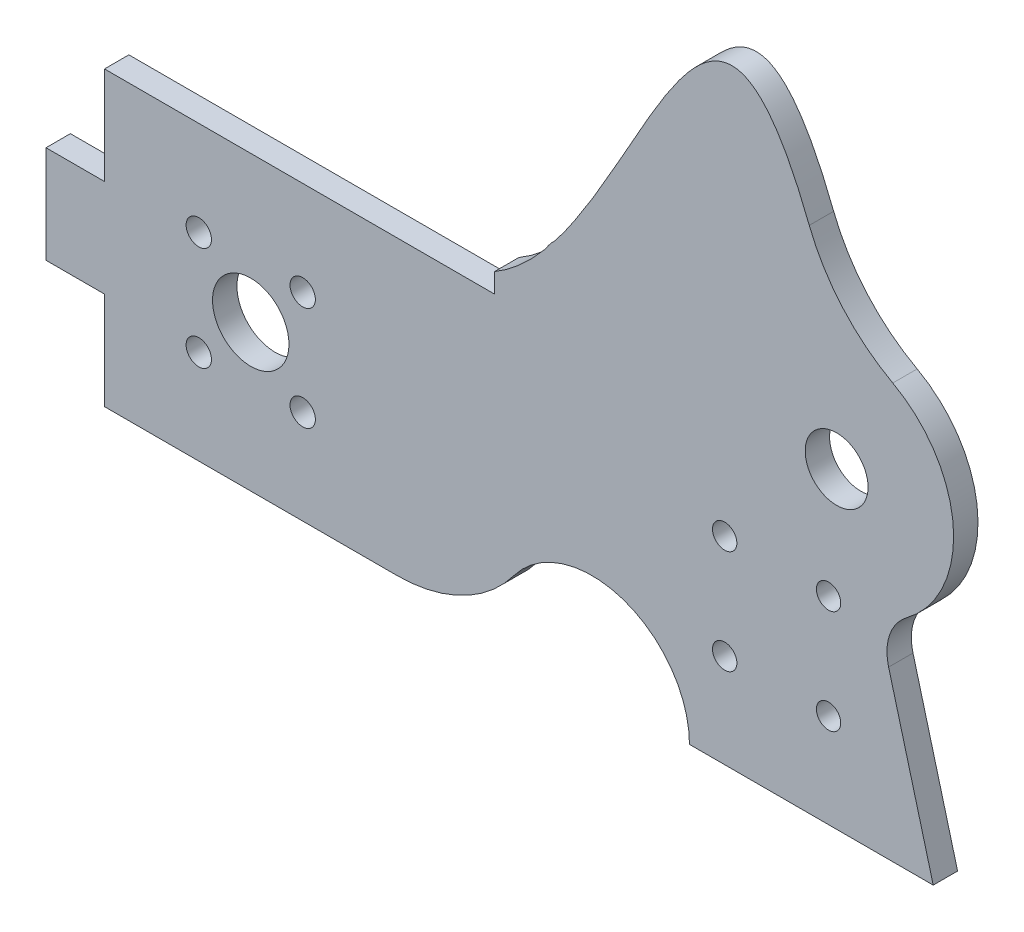
SolidWorks part; units mm, degrees
ref_plane "Front Plane" through (0, 0, 0) normal (0, 0, 1) x (1, 0, 0)
ref_plane "Top Plane" through (0, 0, 0) normal (0, 1, 0) x (1, 0, 0)
ref_plane "Right Plane" through (0, 0, 0) normal (1, 0, 0) x (0, 0, -1)
sketch "Sketch1" plane through (0, 0, 0) normal (0, 0, 1) x (1, 0, 0)
  line L0 (0, 0) -> (107.95, 0)
  line L3 (0, 38.1) -> (0, 25.4)
  line L4 (95.3675, 55.88) -> (0, 38.1)
  line L5 (0, 19.05) -> (100.2273, 19.05) construction
  line L6 (19.05, 19.05) -> (19.05, 28.62) construction
  line L7 (19.05, 19.05) -> (25.817, 25.817) construction
  line L8 (107.95, 0) -> (100.9363, 26.1756)
  line L10 (0, 12.7) -> (0, 0)
  line L11 (0, 25.4) -> (-7.62, 25.4)
  line L13 (0, 12.7) -> (-7.62, 12.7)
  line L14 (-7.62, 25.4) -> (-7.62, 12.7)
  line L15 (100.9363, 26.1756) -> (100.8688, 26.4276)
  arc A0 (100.8688, 26.4276) -> (95.3675, 55.88) centre (95.3675, 40.64) ccw
  circle A1 centre (95.3675, 40.64) radius 4.0957
  circle A2 centre (19.05, 19.05) radius 9.57 construction
  circle A3 centre (25.817, 25.817) radius 1.651
  circle A4 centre (25.817, 12.283) radius 1.651
  circle A5 centre (12.283, 12.283) radius 1.651
  circle A6 centre (12.283, 25.817) radius 1.651
  point P26 (19.05, 19.05)
  dimension "D1" = 8.1915
  dimension "D5" = 15.24
  dimension "D4" = 19.14
  dimension "D7" = 3.302
  dimension "D11" = 97.0107
  dimension "D2" = 38.1
  dimension "D3" = 40.64
  dimension "D6" = 107.95
  dimension "D8" = 45
  dimension "D9" = 4
  dimension "D10" = 19.05
  dimension "D12" = 75
  dimension "D14" = 12.7
  dimension "D15" = 12.7
  dimension "D16" = 7.62
extrude "Boss-Extrude1" add sketch "Sketch1" along normal blind 3.175
sketch "Sketch2" plane through (0, 0, 3.175) normal (0, 0, 1) x (1, 0, 0)
  circle A0 centre (95.3675, 40.64) radius 38.1 construction
sketch "Sketch6" plane through (0, 0, 3.175) normal (0, 0, 1) x (1, 0, 0)
  line L0 (0, 0) -> (107.95, 0) construction
  line L1 (50.8, 0) -> (76.2, 0)
  arc A0 (76.2, 0) -> (50.8, 0) centre (63.5, 0) ccw
  dimension "D1" = 25.4
  dimension "D2" = 31.75
extrude "Cut-Extrude2" cut sketch "Sketch6" against normal blind 6.35
sketch "Sketch7" plane through (0, 0, 3.175) normal (0, 0, 1) x (1, 0, 0)
  line L0 (12.283, 25.817) -> (25.817, 12.283) construction
  line L1 (12.283, 12.283) -> (25.817, 25.817) construction
  circle A0 centre (19.05, 19.05) radius 4.9784
  circle A2 centre (80.7829, 12.2536) radius 1.5875
  circle A3 centre (94.316, 12.2536) radius 1.5875
  circle A4 centre (80.7829, 25.7876) radius 1.5875
  circle A5 centre (94.316, 25.7876) radius 1.5875
  dimension "D1" = 9.9568
extrude "Cut-Extrude3" cut sketch "Sketch7" against normal through all
fillet "Fillet1" radius 6.35 1 edges at (100.8688, 26.4276, 1.5875)
sketch "Sketch8" plane through (0, 0, 3.175) normal (0, 0, 1) x (1, 0, 0)
  line L1 (0, 38.1) -> (50.8, 38.1)
  line L2 (0, 38.1) -> (0, 50.8)
  line L3 (0, 50.8) -> (50.8, 50.8)
  line L4 (50.8, 38.1) -> (50.8, 50.8)
  dimension "D1" = 50.8
  dimension "D2" = 12.7
extrude "Cut-Extrude4" cut sketch "Sketch8" against normal blind 50.8
sketch "Sketch9" plane through (0, 0, 3.175) normal (0, 0, 1) x (1, 0, 0)
  line L3 (50.8, 40.64) -> (57.15, 40.64)
  line L5 (57.15, 40.64) -> (50.8, 40.64)
  line L6 (57.15, 40.64) -> (57.15, 50.8)
  line L7 (57.15, 50.8) -> (50.8, 50.8)
  line L8 (50.8, 40.64) -> (50.8, 50.8)
  line L9 (0, 38.1) -> (50.8, 38.1) construction
  line M8 (50.8, 47.571) -> (50.8, 38.1)
  line M21 (95.3675, 55.88) -> (50.8, 47.571)
  dimension "D1" = 10.16
  dimension "D2" = 2.54
  dimension "D3" = 6.35
extrude "Cut-Extrude5" cut sketch "Sketch9" against normal blind 19.304 contours L3 L6 M21 M8 region at (54.0583, 44.4092, 3.175)
fillet "Fillet6" radius 6.35 1 edges at (57.15, 40.64, 1.5875)
fillet "Fillet7" radius 6.35 1 edges at (57.15, 48.7549, 1.5875)
fillet "Fillet8" radius 19.05 1 edges at (50.8, 0, 1.5875)
sketch "Sketch12" plane through (0, 0, 3.175) normal (0, 0, 1) x (1, 0, 0)
  line L0 (107.95, 0) -> (146.812, 0) construction
  line L1 (8.0257, 45.4128) -> (80.6683, 75.7903) construction
  line L2 (95.3675, 40.64) -> (80.6683, 75.7903) construction
  line L3 (80.6683, 75.7903) -> (79.4434, 78.7195) construction
  line L4 (50.8, 40.64) -> (85.0271, 40.64)
  line L5 (85.0271, 40.64) -> (95.3675, 55.88)
  arc A0 (61.8128, 49.6242) -> (56.8883, 45.1859) centre (62.9766, 43.3817) ccw construction
  circle A1 centre (19.05, 19.05) radius 28.575 construction
  circle A2 centre (95.3675, 40.64) radius 38.1 construction
  circle A3 centre (80.6683, 75.7903) radius 3.175 construction
  spline S0 degree 3 poles (50.8, 40.64) (70.7778, 52.1788) (78.5943, 111.5434) (95.3675, 55.88) knots 0 0 0 0 1 1 1 1
  dimension "D2" = 6.35
  dimension "D1" = 38.862
extrude "Boss-Extrude2" add sketch "Sketch12" against normal blind 3.175
fillet "Fillet9" radius 24.13 1 edges at (95.3675, 55.88, 1.5875)
